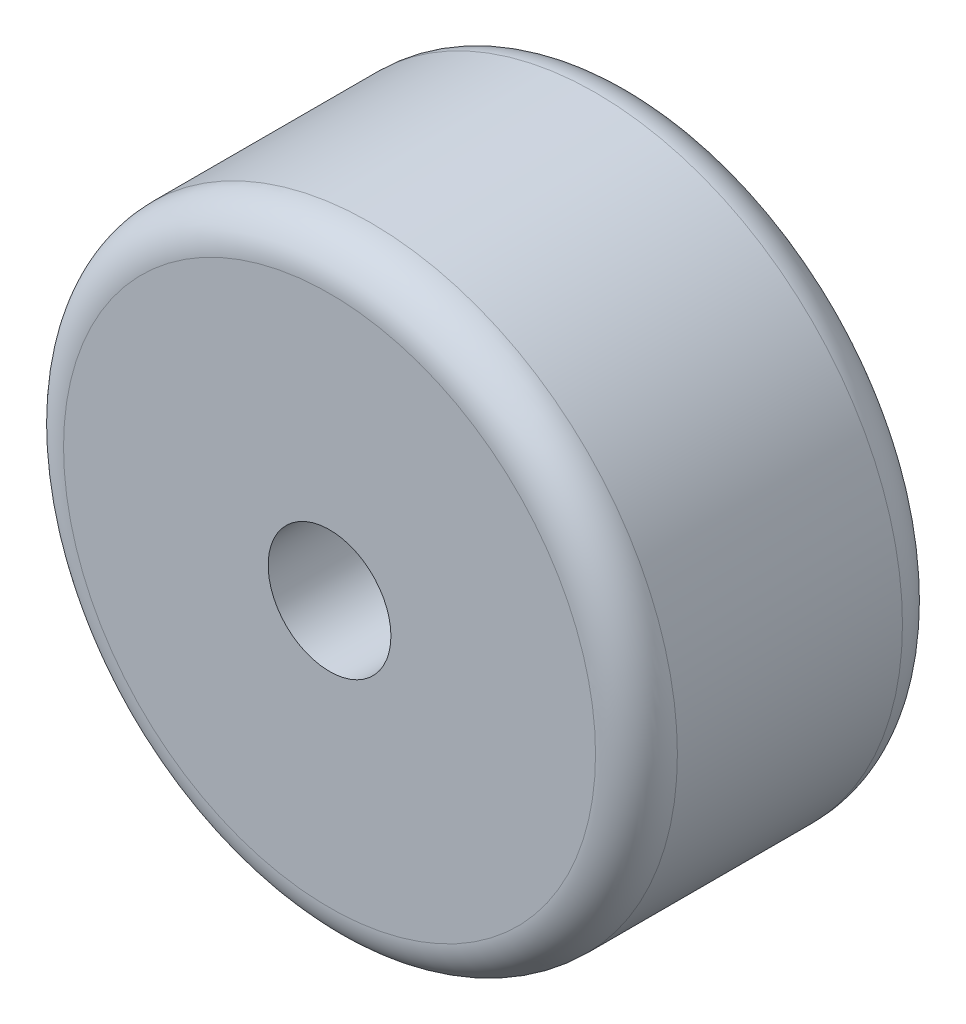
SolidWorks part; units mm, degrees
ref_plane "Front Plane" through (0, 0, 0) normal (0, 0, 1) x (1, 0, 0)
ref_plane "Top Plane" through (0, 0, 0) normal (0, 1, 0) x (1, 0, 0)
ref_plane "Right Plane" through (0, 0, 0) normal (1, 0, 0) x (0, 0, -1)
sketch "Sketch1" plane through (0, 0, 0) normal (0, 0, 1) x (1, 0, 0)
  circle A0 centre (0, 0) radius 150
  dimension "D1" = 300
extrude "Boss-Extrude1" add sketch "Sketch1" along normal blind 150
sketch "Sketch2" plane through (0, 0, 150) normal (0, 0, 1) x (1, 0, 0)
  circle A0 centre (0, 0) radius 30
  dimension "D1" = 60
extrude "Cut-Extrude1" cut sketch "Sketch2" against normal blind 50
fillet "Fillet1" radius 20 2 edges at (150, 0, 150) (150, 0, 0)
sketch "Sketch3" plane through (0, 0, 0) normal (0, 0, -1) x (-1, 0, 0)
  circle A0 centre (0, 0) radius 10
  dimension "D1" = 20
extrude "Cut-Extrude2" cut sketch "Sketch3" against normal blind 5
fillet "Fillet4" radius 50 1 edges at (-10, 0, 0)
